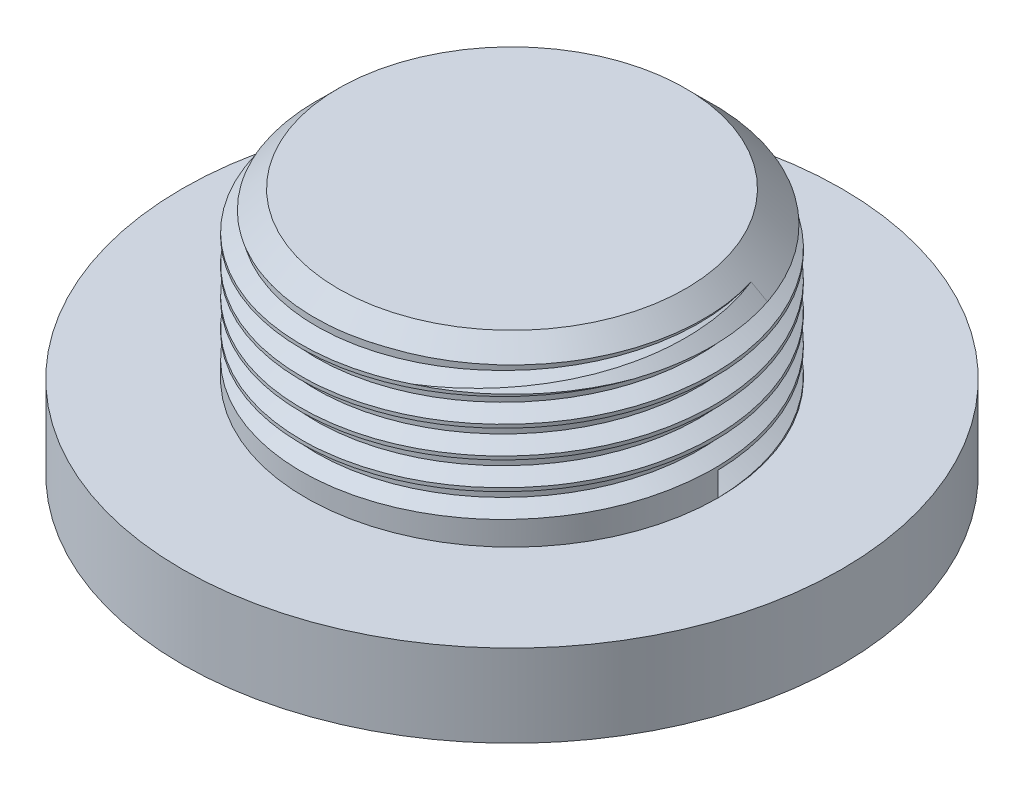
SolidWorks part; units mm, degrees
ref_plane "Front Plane" through (0, 0, 0) normal (0, 0, 1) x (1, 0, 0)
ref_plane "Top Plane" through (0, 0, 0) normal (0, 1, 0) x (1, 0, 0)
ref_plane "Right Plane" through (0, 0, 0) normal (1, 0, 0) x (0, 0, -1)
sketch "Sketch2" plane through (0, 0, 0) normal (0, 1, 0) x (1, 0, 0)
  circle A0 centre (0, 0) radius 25.4
  circle A1 centre (0, 0) radius 15.875
  dimension "D1" = 50.8
  dimension "D2" = 31.75
extrude "Boss-Extrude1" add sketch "Sketch2" along normal blind 12.7 contours A1 region at (0, 0, 0)
extrude "Boss-Extrude2" add sketch "Sketch2<3>" against normal blind 6.35 separate body contours A1 | A0 A1 region at (-24.6816, 0, 0) region at (0, 0, 0)
sketch "Sketch2<3>" plane through (0, 0, 0) normal (0, 1, 0) x (1, 0, 0) same geometry as "Sketch2"
sketch "Sketch4" plane through (0, -6.35, 0) normal (0, -1, 0) x (1, 0, 0)
  line L0 (0, -27.94) -> (0, 27.94) construction
  line L1 (0, -9.2376) -> (8, -4.6188)
  line L2 (8, -4.6188) -> (8, 4.6188)
  line L3 (8, 4.6188) -> (0, 9.2376)
  line L4 (0, 9.2376) -> (-8, 4.6188)
  line L5 (-8, 4.6188) -> (-8, -4.6188)
  line L6 (-8, -4.6188) -> (0, -9.2376)
  circle A0 centre (0, 0) radius 8 construction
  dimension "D1" = 16
extrude "Cut-Extrude2" cut sketch "Sketch4" against normal blind 7
chamfer "Chamfer1" distance 2.5 angle 45 1 edges at (0, 12.7, 15.875)
thread "Thread1" pitch 2.1167 method cut profile "Thread Profile1" start angle 0, offset 0, length 0, pitch 2.1167, diameter 31.75
ref_plane "Plane1" through (15.875, 0, 0) normal (0, 0, 1) x (1, 0, 0)
sketch "Thread Profile1" plane through (15.875, 0, 0) normal (0, 0, 1) x (1, 0, 0)
  line L0 (0, 0) -> (0, 2.1167) construction
  line L11 (0, 0) -> (0, 1.8521)
  line L12 (0, 1.8521) -> (-1.1457, 1.1906)
  line L13 (-1.1457, 1.1906) -> (-1.1457, 0.6615)
  line L15 (-1.1457, 0.6615) -> (0, 0)
  line L17 (-1.1457, 0.926) -> (0, 0.926) construction
  point P2 (0, 0)
  dimension "Pitch" = 2.1167
  dimension "Profile_Angle" = 60
  dimension "Profile_Land" = 0.5292
  dimension "Profile_Height" = 1.1457
